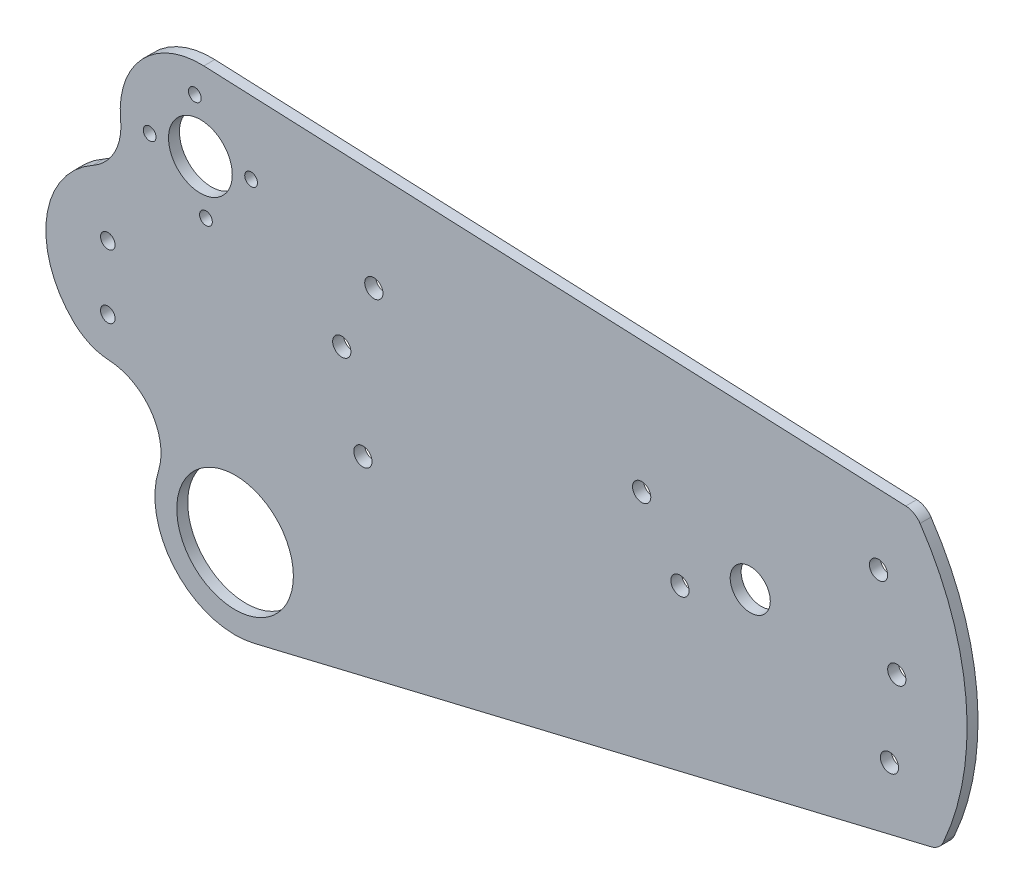
SolidWorks part; units mm, degrees
ref_plane "Front Plane" through (0, 0, 0) normal (0, 0, 1) x (1, 0, 0)
ref_plane "Top Plane" through (0, 0, 0) normal (0, 1, 0) x (1, 0, 0)
ref_plane "Right Plane" through (0, 0, 0) normal (1, 0, 0) x (0, 0, -1)
sketch "Sketch1" plane through (0, 0, 0) normal (0, 0, 1) x (1, 0, 0)
  line L0 (84.9145, -33.5) -> (-137.2004, -33.5) construction
  line L1 (-111.9507, 49.4797) -> (80.6734, 41.2065)
  line L2 (-115.3158, 49.6243) -> (-100.9557, -81.605) construction
  line L3 (-97.7015, -80.7362) -> (92.4727, -29.9601) construction
  line L4 (76.721, 41.3762) -> (84.7527, -32.0213) construction
  line L5 (-108.1357, -15.9904) -> (80.7368, 4.6775) construction
  line L6 (91, -33.5) -> (-88.5, -33.5) construction
  line L7 (-97.4673, 5.5) -> (-155.3054, 5.5) construction
  line L8 (-138.3, -14) -> (-155.3054, -14) construction
  line L9 (-138.3, 5.5) -> (-138.3, -33.5) construction
  line L10 (-155.3054, 5.5) -> (-155.3054, -33.5) construction
  line L11 (37.992, 33.5) -> (37.992, -33.5) construction
  line L12 (-108.1357, -83.2449) -> (87.5998, -36.3241)
  line L13 (-91.5, 33.5) -> (88, 33.5) construction
  line L14 (-68.3, -21.5) -> (-107.0686, -25.7423) construction
  circle A0 centre (37.992, 0) radius 5.5
  circle A1 centre (-112.8948, 27.5) radius 14 construction
  circle A2 centre (-103.3767, -59.4808) radius 14 construction
  arc A3 (-91.5, 33.5) -> (-88.5, -33.5) centre (-18.0922, 3.2198) ccw construction
  circle A4 centre (-68.3, -21.5) radius 2.5
  circle A5 centre (-68.3, -21.5) radius 2.5 construction
  circle A6 centre (-138.3, -5.25) radius 2
  circle A7 centre (-138.3, -22.75) radius 2
  arc A8 (-142.4281, 10.607) -> (-147.5429, -29.3643) centre (-130.3054, -11.2571) ccw
  arc A9 (-147.5429, -29.3643) -> (-137.2004, -33.5) centre (-137.2004, -18.5) ccw
  circle A10 centre (-112.8948, 27.5) radius 22
  arc A11 (87.5998, -36.3241) -> (91, -33.5) centre (86.4343, -31.4619) ccw
  circle A12 centre (-103.3767, -59.4808) radius 22
  arc A13 (91, -33.5) -> (84.5968, 39.0177) centre (22.6589, -2.9929) ccw
  arc A14 (91, -33.5) -> (88, 33.5) centre (22.6589, -2.9929) ccw construction
  arc A15 (84.5968, 39.0177) -> (80.6734, 41.2065) centre (80.4588, 36.2111) ccw
  arc A17 (-124.3786, -52.9294) -> (-137.9492, -33.4813) centre (-138.698, -48.4626) ccw
  arc A18 (-142.4281, 10.607) -> (-134.78, 25.2557) centre (-149.7017, 23.7254) ccw
  circle A19 centre (-74.1, 1.7) radius 2.5
  circle A20 centre (-65.3, 20) radius 2.5
  circle A21 centre (8.2, 8.3) radius 2.5
  circle A23 centre (18.7, -8.7) radius 2.5
  circle A25 centre (78.2, -0.1) radius 2.5
  circle A26 centre (76.2, -22) radius 2.5
  circle A27 centre (73.2, 22.3) radius 2.5
  circle A28 centre (73.2, 22.3) radius 2.5 construction
  circle A29 centre (78.2, -0.1) radius 2.5 construction
  circle A31 centre (8.2, 8.3) radius 2.5 construction
  circle A32 centre (18.7, -8.7) radius 2.5 construction
  circle A33 centre (76.2, -22) radius 2.5 construction
  circle A34 centre (-74.1, 1.7) radius 2.5 construction
  circle A35 centre (-65.3, 20) radius 2.5 construction
  circle A36 centre (-114.4176, 41.4169) radius 1.75
  circle A37 centre (-98.9778, 29.0229) radius 1.75
  circle A38 centre (-111.3719, 13.5831) radius 1.75
  circle A39 centre (-126.8117, 25.9771) radius 1.75
  circle A40 centre (-104.8996, -45.5639) radius 1.75
  circle A41 centre (-89.4597, -57.9579) radius 1.75
  circle A42 centre (-101.8538, -73.3977) radius 1.75
  circle A43 centre (-117.2936, -61.0037) radius 1.75
  circle A44 centre (37.992, 0) radius 35 construction
  circle A45 centre (37.992, 0) radius 43
  circle A49 centre (-103.3767, -59.4808) radius 16
  circle A50 centre (-112.8948, 27.5) radius 16 construction
  circle A51 centre (-112.8948, 27.5) radius 8.75
  circle A52 centre (-103.3767, -59.4808) radius 8.75
  arc A53 (91, -33.5) -> (88, 33.5) centre (22.6589, -2.9929) ccw construction
  point P44 (0, 0)
  point P46 (0, 0)
  point P52 (80.7368, 4.6775)
  point P70 (-111.638, -83.6744)
  point P71 (0, 0)
  point P84 (0, 0)
  point P85 (0, 0)
  point P109 (-112.8948, 27.5)
  point P118 (-103.3767, -59.4808)
  dimension "D5" = 4
  dimension "D6" = 25
  dimension "D9" = 15
  dimension "D13" = 10
  dimension "D14" = 28
  dimension "D11" = 44
  dimension "D15" = 3.5
  dimension "D12" = 70
  dimension "D19" = 11
  dimension "D20" = 17.5
  dimension "D22" = 32
  dimension "D2" = 39
  dimension "D3" = 70
  dimension "D4" = 17.5
  dimension "D7" = 14
  dimension "D8" = 10
  dimension "D10" = 87.5
  dimension "D21" = 190
  dimension "D23" = 39
  dimension "D18" = 8
  dimension "D16" = 4
  dimension "D17" = 4
extrude "Boss-Extrude1" add sketch "Sketch1" along normal blind 3 contours A45 A0 A25 A26 A27 | A45 L1 A10 A18 A8 A9 A17 A12 L3 A23 A21 A20 A19 A7 A6 A4 | A10 A39 A38 A37 A36 | A12 A49 region at (58.0062, 36.6785, 0) region at (-43.3827, -9.8812, 0) region at (-97.4575, 42.2885, 0) region at (-100.1569, -38.3469, 0)
